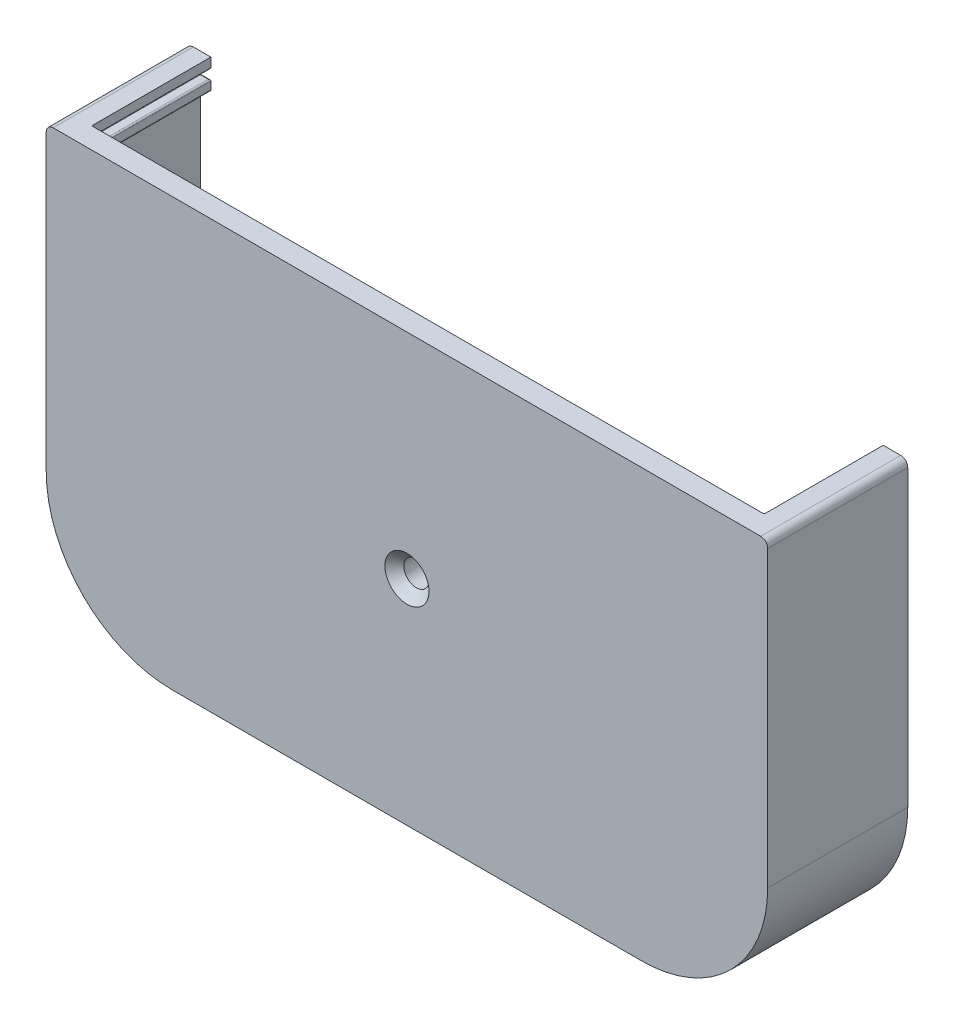
SolidWorks part; units mm, degrees
ref_plane "Plan de face" through (0, 0, 0) normal (0, 0, 1) x (1, 0, 0)
ref_plane "Plan de dessus" through (0, 0, 0) normal (0, 1, 0) x (1, 0, 0)
ref_plane "Plan de droite" through (0, 0, 0) normal (1, 0, 0) x (0, 0, -1)
sketch "Esquisse1" plane through (0, 0, 0) normal (0, 0, 1) x (1, 0, 0)
  line L1 (-33.5, -30.5) -> (33.5, -30.5)
  line L2 (-51.5, -12.5) -> (-51.5, 30.5)
  line L3 (-51.5, 30.5) -> (51.5, 30.5)
  line L4 (51.5, -12.5) -> (51.5, 30.5)
  line L5 (-51.5, -30.5) -> (51.5, 30.5) construction
  line L6 (-51.5, 30.5) -> (51.5, -30.5) construction
  arc A0 (33.5, -30.5) -> (51.5, -12.5) centre (33.5, -12.5) ccw
  arc A1 (-33.5, -30.5) -> (-51.5, -12.5) centre (-33.5, -12.5) cw
  point P0 (0, 0)
  dimension "D3" = 18
  dimension "D1" = 61
  dimension "D2" = 103
extrude "Boss.-Extru.1" add sketch "Esquisse1" along normal blind 20
sketch "Esquisse2" plane through (0, 0, 0) normal (0, 0, -1) x (-1, 0, 0)
  line L0 (-51.5, 30.5) -> (51.5, 30.5) construction
  line L1 (-49.5, 29) -> (-48, 29)
  line L2 (-49.5, 29) -> (-49.5, 27.75)
  line L3 (-49.5, 27.75) -> (49.5, 27.75)
  line L4 (49.5, 29) -> (49.5, 27.75)
  line L5 (48, 29) -> (49.5, 29)
  line L6 (-51.5, -12.5) -> (-51.5, 30.5) construction
  line L7 (-48, 29) -> (-48, 30.5)
  line L8 (-48, 30.5) -> (48, 30.5)
  line L9 (48, 29) -> (48, 30.5)
  line L10 (51.5, 30.5) -> (51.5, -12.5) construction
  point P4 (0, 28.5)
  point P12 (0, 30.5)
  dimension "D1" = 2
  dimension "D2" = 1.25
  dimension "D3" = 1.5
  dimension "D4" = 3.5
  dimension "D5" = 2
extrude "Enlèv. mat.-Extru.1" cut sketch "Esquisse2" against normal offset from surface (18 mm away) 2 up to face at (0, -5.4093, 20)
shell "Coque2" thickness 2 removed face at (0, 14.2889, 0)
sketch "Esquisse14" plane through (0, 0, 18) normal (0, 0, -1) x (-1, 0, 0)
  line L1 (-48, 30.5) -> (48, 30.5)
  line L2 (-48, 30.5) -> (-48, 29)
  line L3 (-48, 29) -> (48, 29)
  line L4 (48, 30.5) -> (48, 29)
extrude "Boss.-Extru.8" add sketch "Esquisse14" along normal blind 1
sketch "Esquisse3" plane through (0, 0, 0) normal (0, 0, -1) x (-1, 0, 0)
  line L0 (-48, 30.5) -> (-48, 29) construction
  line L1 (48, 29) -> (48, 30.5) construction
  line L2 (49.5, 25.75) -> (-49.5, 25.75) construction
  line L3 (-48, 27.75) -> (48, 27.75)
  line L4 (-48, 27.75) -> (-48, 25.75)
  line L5 (-48, 25.75) -> (48, 25.75)
  line L6 (48, 27.75) -> (48, 25.75)
  line L7 (49.5, 27.75) -> (-49.5, 27.75) construction
extrude "Enlèv. mat.-Extru.2" cut sketch "Esquisse3" against normal up to surface (17 mm away) up to face at (0, 29.75, 17)
sketch "Esquisse4" plane through (0, 0, 18) normal (0, 0, -1) x (-1, 0, 0)
  line L0 (0, 30.5) -> (0, -30.5) construction
  line L1 (-48, 30.5) -> (48, 30.5) construction
  line L2 (33.5, -30.5) -> (-33.5, -30.5) construction
  circle A0 centre (0, 0) radius 2.794
  dimension "D1" = 5.588
extrude "Boss.-Extru.2" add sketch "Esquisse4" along normal up to surface (18 mm away) up to face at (0, 11.2465, 0)
sketch "Esquisse5" plane through (0, 0, 0) normal (0, 0, -1) x (-1, 0, 0)
  circle A0 centre (0, 0) radius 1
  dimension "D1" = 2
extrude "Enlèv. mat.-Extru.3" cut sketch "Esquisse5" against normal blind 5
sketch "Esquisse7" plane through (0, 0, 18) normal (0, 0, -1) x (-1, 0, 0)
  line L0 (0, 10.92) -> (0, -16.55) construction
  line L1 (35, -28.4295) -> (49.375, -14.4961)
  line L2 (-35, -28.4295) -> (-49.375, -14.4961)
  arc A1 (35, -28.4295) -> (49.375, -14.4961) centre (33.5, -12.5) ccw
  arc A2 (33.5, -28.5) -> (49.5, -12.5) centre (33.5, -12.5) ccw construction
  arc A3 (33.5, -28.5) -> (49.5, -12.5) centre (33.5, -12.5) ccw construction
  arc A4 (-35, -28.4295) -> (-49.375, -14.4961) centre (-33.5, -12.5) cw
  dimension "D1" = 35
  dimension "D2" = 14.375
extrude "Boss.-Extru.4" add sketch "Esquisse7" along normal up to surface (18 mm away) up to face at (0, 11.2465, 0)
sketch "Esquisse8" plane through (0, 0, 0) normal (0, 0, -1) x (-1, 0, 0)
  line L0 (33.5, -30.5) -> (-33.5, -30.5) construction
  line L1 (-51.5, -12.5) -> (-51.5, 30.5) construction
  line L2 (0, 0) -> (0, -22.552) construction
  circle A0 centre (-44, -23) radius 1
  circle A1 centre (44, -23) radius 1
  dimension "D3" = 2
  dimension "D1" = 7.5
  dimension "D2" = 7.5
extrude "Boss.-Extru.5" add sketch "Esquisse8" along normal blind 3
fillet "Congé5" radius 0.5 4 edges at (-43, -23, 0) (43, -23, 0) (-43, -23, -3) (43, -23, -3)
fillet "Congé6" radius 1 2 edges at (-51.5, 30.5, 10) (51.5, 30.5, 10)
sketch "Esquisse9" plane through (0, 0, 0) normal (0, 0, -1) x (-1, 0, 0)
  line L0 (49.5, 25.75) -> (49.5, -12.5) construction
  line L1 (-49.5, 25.75) -> (49.5, 25.75)
  line L2 (-49.5, 25.75) -> (-49.5, 26.25)
  line L3 (-49.5, 26.25) -> (49.5, 26.25)
  line L4 (49.5, 25.75) -> (49.5, 26.25)
  dimension "D1" = 0.5
extrude "Enlèv. mat.-Extru.4" cut sketch "Esquisse9" against normal up to surface (18 mm away) up to face at (0, 28.375, 18)
fillet "Congé8" radius 0.2 30 edges at (-48, 27.75, 8.5) (-48.75, 29, 0) (-48.75, 27.75, 0) (48.75, 27.75, 0) (48.75, 29, 0) (-48, 29, 8.5) (0, 27.75, 17) (-49.5, 29, 9) (-49.5, 28.375, 0) (-49.5, 27.75, 9) (49.5, 27.75, 9) (49.5, 28.375, 0) (49.5, 29, 9) (0, 27.75, 18) (49.5, 28.375, 18) (0, 29, 18) (-49.5, 28.375, 18) (0, 26.25, 18) (-48, 29.75, 17) (-48, 27, 17) (-48, 26.25, 8.5) (-49.5, 26.25, 9) (48, 27, 17) (0, 26.25, 17) (48, 29.75, 17) (0, 29, 17) (48, 29, 8.5) (48, 27.75, 8.5) (48, 26.25, 8.5) (49.5, 26.25, 9)
hole_wizard "CSK for M3 Flat Head Machine Screw1" positions "Esquisse16" profile "Esquisse15" countersink size "M3" standard "Ansi Metric" end condition through all
sketch "Esquisse16" plane through (0, 0, 20) normal (0, 0, 1) x (1, 0, 0)
  point P1 (0, 0)
sketch "Esquisse15" plane through (0, 0, 20) normal (1, 0, 0) x (0, -1, 0)
  line L0 (0, 0) -> (0, 23)
  line L1 (0, 23) -> (1.8, 23)
  line L2 (1.8, 23) -> (1.8, 1.35)
  line L3 (1.8, 1.35) -> (3.15, 0)
  line L5 (3.15, 0) -> (0, 0)
  line L6 (-1.8, 1.35) -> (-3.15, 0) construction
  line L11 (0, -6.35) -> (0, 107.95) construction
  dimension "Diamètre du perçage jusqu'au prochain" = 3.6
  dimension "Profondeur du perçage jusqu'au prochain" = 23
  dimension "Diamètre du fraisage entrant" = 6.3
  dimension "Angle du fraisage entrant" = 90
fillet "Congé9" radius 5 1 edges at (-2.794, 0, 18)
fillet "Fillet1" radius 2 15 edges at (-49.4414, 26.1914, 17.9414) (49.4414, 26.1914, 17.9414) (49.4687, -13.5, 18) (-49.4687, -13.5, 18) (-34.2508, -28.4824, 18) (34.2508, -28.4824, 18) (35, -28.4295, 9) (49.375, -14.4961, 9) (-49.375, -14.4961, 9) (-35, -28.4295, 9) (49.5, 6.775, 18) (42.1875, -21.4628, 18) (-49.5, 6.775, 18) (-42.1875, -21.4628, 18) (0, -28.5, 18)
sketch "Sketch1" plane through (0, 0, 0) normal (0, 0, -1) x (-1, 0, 0)
  circle A0 centre (0, 0) radius 2.794
extrude "Cut-Extrude1" cut sketch "Sketch1" against normal blind 0.5
